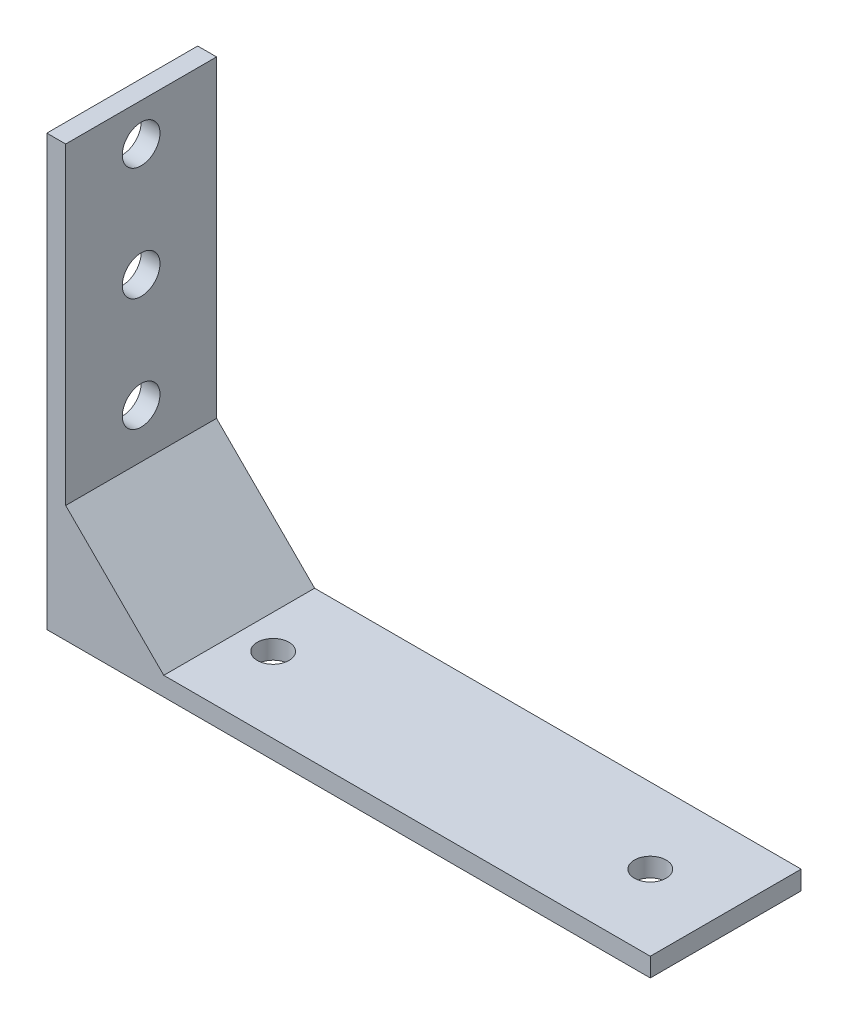
SolidWorks part; units mm, degrees
ref_plane "Front Plane" through (0, 0, 0) normal (0, 0, 1) x (1, 0, 0)
ref_plane "Top Plane" through (0, 0, 0) normal (0, 1, 0) x (1, 0, 0)
ref_plane "Right Plane" through (0, 0, 0) normal (1, 0, 0) x (0, 0, -1)
sketch "Sketch1" plane through (0, 0, 0) normal (0, 0, 1) x (1, 0, 0)
  line L1 (0, 0) -> (3.175, 0)
  line L2 (0, 0) -> (0, 72.39)
  line L3 (0, 72.39) -> (3.175, 72.39)
  line L4 (3.175, 3.175) -> (3.175, 72.39)
  line L5 (0, 0) -> (101.6, 0)
  line L6 (0, 0) -> (0, 3.175)
  line L7 (3.175, 3.175) -> (101.6, 3.175)
  line L8 (101.6, 0) -> (101.6, 3.175)
  dimension "D1" = 101.6
  dimension "D2" = 3.175
  dimension "D3" = 3.175
  dimension "D4" = 72.39
extrude "Boss-Extrude1" add sketch "Sketch1" along normal blind 25.4 contours L5 L8 L7 L4 L3 L2 L1 region at (1.2475, 1.5875, 0)
sketch "Sketch2" plane through (0, 3.175, 0) normal (0, 1, 0) x (1, 0, 0)
  line L0 (101.6, -25.4) -> (101.6, 0) construction
  line L1 (3.175, -25.4) -> (101.6, -25.4) construction
  circle A0 centre (88.9, -12.7) radius 2.667
  circle A1 centre (25.4, -12.7) radius 2.667
  dimension "D5" = 5.334
  dimension "D6" = 5.334
  dimension "D2" = 63.5
  dimension "D1" = 12.7
  dimension "D3" = 12.7
  dimension "D4" = 12.7
extrude "Cut-Extrude1" cut sketch "Sketch2" against normal blind 25.4
sketch "Sketch3" plane through (0, 0, 0) normal (-1, 0, 0) x (0, 0, 1)
  line L0 (25.4, 0) -> (0, 0) construction
  line L2 (0, 3.175) -> (0, 72.39) construction
  circle A0 centre (12.7, 27.94) radius 3.175
  circle A1 centre (12.7, 46.99) radius 3.175
  circle A2 centre (12.7, 66.04) radius 3.175
  dimension "D1" = 6.35
  dimension "D2" = 6.35
  dimension "D3" = 6.35
  dimension "D4" = 27.94
  dimension "D5" = 19.05
  dimension "D6" = 19.05
  dimension "D7" = 12.7
  dimension "D8" = 12.7
  dimension "D9" = 12.7
extrude "Cut-Extrude2" cut sketch "Sketch3" against normal through all
sketch "Sketch4" plane through (0, 0, 25.4) normal (0, 0, 1) x (1, 0, 0)
  line L0 (3.175, 19.685) -> (19.685, 3.175)
  line L1 (3.175, 3.175) -> (3.175, 72.39) construction
  line L2 (3.175, 3.175) -> (101.6, 3.175) construction
  line L3 (19.685, 3.175) -> (3.175, 3.175)
  line L4 (3.175, 3.175) -> (3.175, 19.685)
  dimension "D1" = 45
  dimension "D2" = 16.51
extrude "Boss-Extrude2" add sketch "Sketch4" against normal blind 25.4
